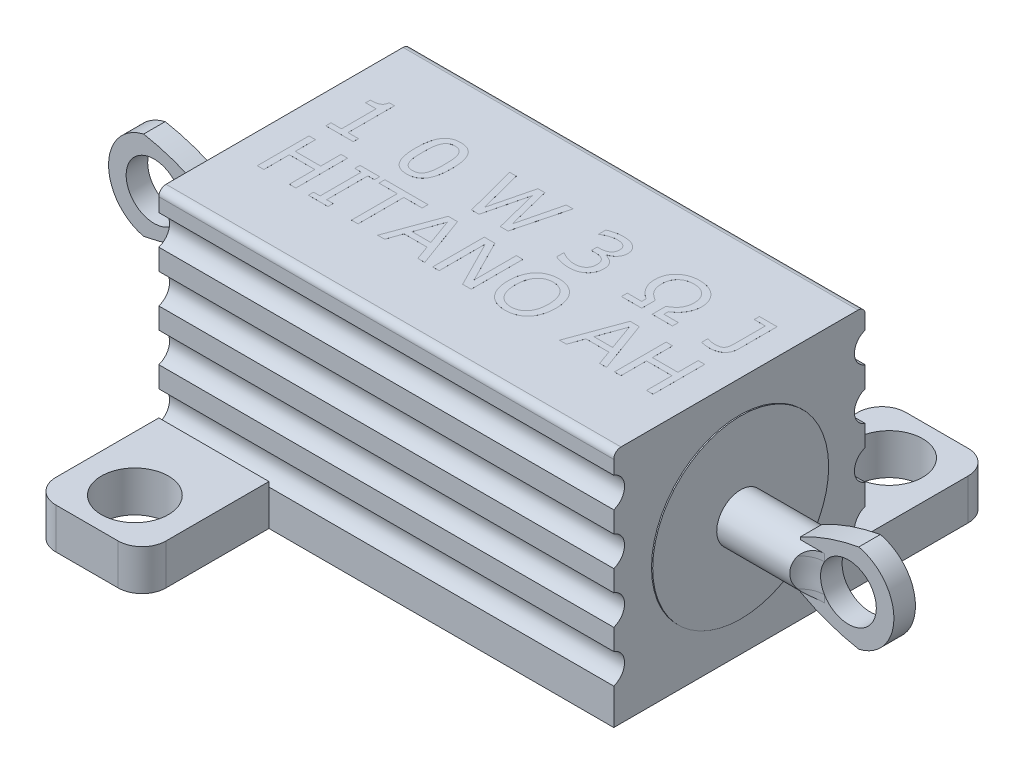
SolidWorks part; units mm, degrees
material "2024-T4"
ref_plane "Front Plane" through (0, 0, 0) normal (0, 0, 1) x (1, 0, 0)
ref_plane "Top Plane" through (0, 0, 0) normal (0, 1, 0) x (1, 0, 0)
ref_plane "Right Plane" through (0, 0, 0) normal (1, 0, 0) x (0, 0, -1)
sketch "Sketch1" plane through (0, 0, 0) normal (1, 0, 0) x (0, 0, -1)
  line L0 (-4.8, 3.5) -> (-4.8, 2.2804) construction
  line L1 (-4.95, 5) -> (4.95, 5)
  line L2 (-5.25, 5) -> (-5.25, -5) construction
  line L3 (-5.25, -5) -> (5.25, -5)
  line L4 (5.25, 4.7) -> (5.25, 4.125)
  line L5 (-5.25, 5) -> (5.25, -5) construction
  line L6 (-5.25, -5) -> (5.25, 5) construction
  line L7 (-5.25, 4.7) -> (-5.25, 4.125)
  line L8 (-5.25, 2.875) -> (-5.25, 2)
  line L9 (-5.25, 0.75) -> (-5.25, -0.125)
  line L10 (-5.25, -1.375) -> (-5.25, -2.25)
  line L11 (-5.25, -3.5) -> (-5.25, -5)
  line L12 (0, 0) -> (0, -1.597) construction
  line L13 (5.25, 4.125) -> (5.25, 2.875) construction
  line L14 (5.25, 2.875) -> (5.25, 2)
  line L15 (5.25, 2) -> (5.25, 0.75) construction
  line L16 (5.25, 0.75) -> (5.25, -0.125)
  line L17 (5.25, -0.125) -> (5.25, -1.375) construction
  line L18 (5.25, -1.375) -> (5.25, -2.25)
  line L19 (5.25, -2.25) -> (5.25, -3.5) construction
  line L20 (5.25, -3.5) -> (5.25, -5)
  arc A0 (-5.25, 4.125) -> (-5.25, 2.875) centre (-5.459, 3.5) cw
  arc A1 (-5.25, 2) -> (-5.25, 0.75) centre (-5.459, 1.375) cw
  arc A2 (-5.25, -0.125) -> (-5.25, -1.375) centre (-5.459, -0.75) cw
  arc A3 (-5.25, -2.25) -> (-5.25, -3.5) centre (-5.459, -2.875) cw
  arc A4 (5.25, -2.25) -> (5.25, -3.5) centre (5.459, -2.875) ccw
  arc A5 (5.25, -0.125) -> (5.25, -1.375) centre (5.459, -0.75) ccw
  arc A6 (5.25, 4.125) -> (5.25, 2.875) centre (5.459, 3.5) ccw
  arc A7 (5.25, 2) -> (5.25, 0.75) centre (5.459, 1.375) ccw
  arc A8 (4.95, 5) -> (5.25, 4.7) centre (4.95, 4.7) cw
  arc A9 (-4.95, 5) -> (-5.25, 4.7) centre (-4.95, 4.7) ccw
  point P0 (0, 0)
  dimension "D3" = 4.8
  dimension "D8" = 0.3
  dimension "D1" = 10
  dimension "D2" = 10.5
  dimension "D4" = 1.5
  dimension "D5" = 1.25
  dimension "D7" = 1.5
  dimension "D6" = 4
extrude "Boss-Extrude1" add sketch "Sketch1" along normal mid plane 19
sketch "Sketch2" plane through (0, -5, 0) normal (0, -1, 0) x (1, 0, 0)
  line L3 (9.5, 5.25) -> (-9.5, 5.25) construction
  line L5 (0, 0) -> (13.2167, 0) construction
  line L6 (0, 7.9538) -> (0, -6.2812) construction
  line L15 (-7.2, 7.15) -> (-12.3723, 7.15) construction
  line L16 (-7.2, -11.3006) -> (-7.2, -4.0961) construction
  line L17 (-10.7974, -7.85) -> (-3.5315, -7.85) construction
  line L18 (9.5, -5.25) -> (-9.5, -5.25) construction
  line L19 (-4.9, 9.55) -> (-4.9, 5.25)
  line L20 (-8.5, 10.55) -> (-5.9, 10.55)
  line L21 (-9.5, 5.25) -> (-9.5, 9.55)
  line L22 (-4.9, 5.25) -> (-9.5, 5.25)
  line L23 (4.9, -9.55) -> (4.9, -5.25)
  line L24 (4.9, -5.25) -> (9.5, -5.25)
  line L25 (9.5, -5.25) -> (9.5, -9.55)
  line L26 (8.5, -10.55) -> (5.9, -10.55)
  line L27 (7.2, -7.15) -> (14.4966, -7.15) construction
  line L28 (-5.8, 8.55) -> (-5.8, 6.0658) construction
  line L29 (9.5, 5.25) -> (9.5, -5.25) construction
  line L30 (5.8, -8.55) -> (5.8, -13.7324) construction
  line L31 (-9.5, 5.25) -> (-9.5, -5.25) construction
  circle A9 centre (-7.2, 8.55) radius 1.4
  arc A10 (-4.9, 9.55) -> (-5.9, 10.55) centre (-5.9, 9.55) ccw
  arc A11 (-9.5, 9.55) -> (-8.5, 10.55) centre (-8.5, 9.55) cw
  circle A12 centre (7.2, -8.55) radius 1.4
  arc A13 (9.5, -9.55) -> (8.5, -10.55) centre (8.5, -9.55) cw
  arc A14 (4.9, -9.55) -> (5.9, -10.55) centre (5.9, -9.55) ccw
  point P13 (4.9, 9.85)
  point P16 (9.5, 9.85)
  point P40 (0, 0)
  point P50 (-4.9, -9.85)
  point P51 (-9.5, -9.85)
  dimension "D3" = 15.8
  dimension "D4" = 12.4
  dimension "D8" = 15.3
  dimension "D9" = 15.3
  dimension "D1" = 12.4
  dimension "D2" = 4.6
  dimension "D5" = 15.8
  dimension "D6" = 14.4
  dimension "D7" = 2.6
  dimension "D10" = 8.55
extrude "Boss-Extrude2" add sketch "Sketch2" against normal blind 1.7
sketch "Sketch3" plane through (0, 0, 0) normal (1, 0, 0) x (0, 0, -1)
  circle A0 centre (0, 0) radius 3.675
  dimension "D1" = 7.35
extrude "Boss-Extrude3" add sketch "Sketch3" along normal mid plane 19.1
sketch "Sketch5" plane through (0, 0, 0) normal (1, 0, 0) x (0, 0, -1)
  circle A0 centre (0, 0) radius 1
  dimension "D1" = 2
extrude "Boss-Extrude4" add sketch "Sketch5" along normal mid plane 25
sketch "Sketch6" plane through (0, 0, 0) normal (0, 0, 1) x (1, 0, 0)
  line L0 (12.5, -1) -> (12.5, 1) construction
  line L1 (-15.6066, 0) -> (23.2797, 0) construction
  line L2 (12.5, 1) -> (12.5, 5.1151) construction
  line L3 (16.4, 0) -> (16.4, 5.4523) construction
  line L4 (10.6512, 1) -> (12.5, 1) construction
  line L5 (12.5, 1) -> (9.55, 1) construction
  line L6 (0, 8.4055) -> (0, -7.6743) construction
  line L7 (12.5, 1) -> (12.5, -1)
  arc A0 (12.5, 1) -> (14.933, 1.85) centre (16.4164, -6.3031) cw
  arc A1 (14.933, 1.85) -> (14.933, -1.85) centre (14.5, 0) cw
  arc A2 (12.5, -1) -> (14.933, -1.85) centre (16.4164, 6.3031) ccw
  circle A3 centre (14.5, 0) radius 1.1649
  dimension "D1" = 3.9
  dimension "D3" = 16.4
  dimension "D2" = 3.7
  dimension "D4" = 2
extrude "Boss-Extrude5" add sketch "Sketch6" along normal mid plane 0.9
mirror "Mirror1" about plane through (0, 0, 0) normal (1, 0, 0) of "Boss-Extrude5"
fillet "Fillet1" radius 1 4 edges at (-12.5, 0, -0.45) (-12.5, 0, 0.45) (12.5, 0, -0.45) (12.5, 0, 0.45)
sketch "Sketch7" plane through (0, 5, 0) normal (0, 1, 0) x (1, 0, 0)
  line L0 (9.5, 0) -> (-9.5, 0) construction
  line L1 (9.5, 4.95) -> (9.5, -4.95) construction
  line L2 (-9.5, 4.95) -> (-9.5, -4.95) construction
  line L3 (9.5, 0.5) -> (-9.5, 0.5) construction
  line L4 (9.5, -2.3734) -> (-9.5, -2.3734) construction
  text T0 "10W3ΩJ" font "Verdana" height in points 8
  text T1 "HITANO AH" font "Verdana" height in points 8
  dimension "D1" = 0.5
extrude "Boss-Extrude6" add sketch "Sketch7" along normal blind 0.001
